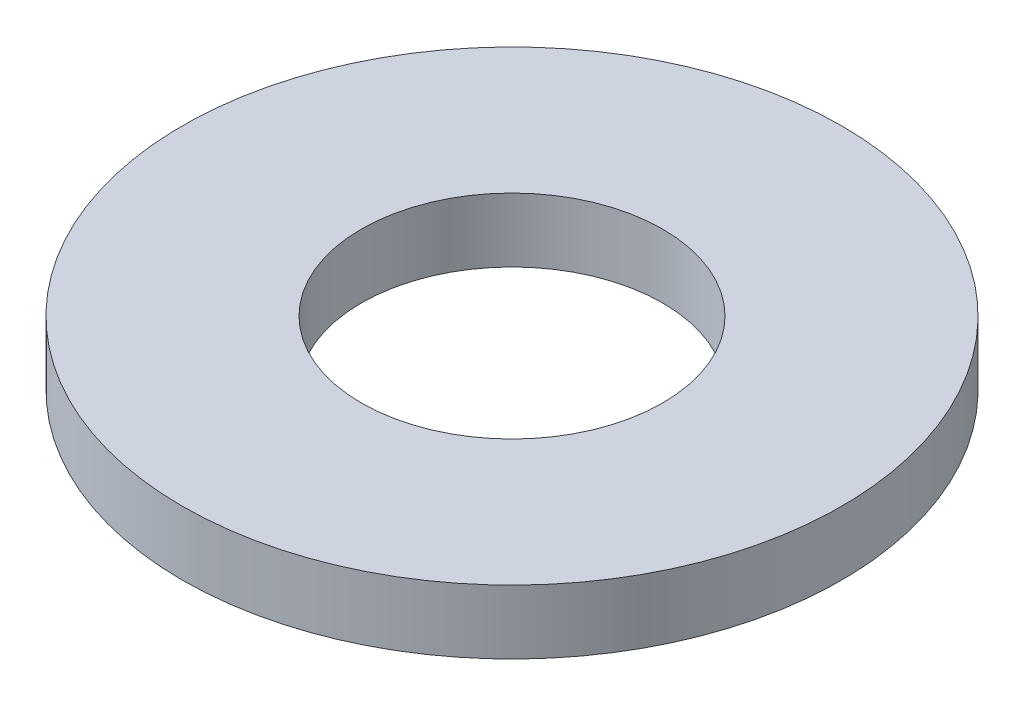
SolidWorks part; units mm, degrees
ref_plane "Front Plane" through (0, 0, 0) normal (0, 0, 1) x (1, 0, 0)
ref_plane "Top Plane" through (0, 0, 0) normal (0, 1, 0) x (1, 0, 0)
ref_plane "Right Plane" through (0, 0, 0) normal (1, 0, 0) x (0, 0, -1)
sketch "Sketch1" plane through (0, 0, 0) normal (0, 1, 0) x (1, 0, 0)
  circle A0 centre (0, 0) radius 87.5
  dimension "FLANGE_OD" = 175
extrude "Boss-Extrude1" add sketch "Sketch1" along normal blind 17
sketch "Sketch2" plane through (0, 0, 0) normal (0, 1, 0) x (1, 0, 0)
  circle A0 centre (0, 0) radius 40
  dimension "BORE_D" = 80
extrude "Cut-Extrude1" cut sketch "Sketch2" along normal through all
sketch "Sketch3" plane through (0, 17, 0) normal (0, 1, 0) x (1, 0, 0)
  circle A0 centre (0, 0) radius 24.5605 construction
  circle A1 centre (-24.5605, 0) radius 7.8849
  dimension "BOLT_D" = 15.7699
  dimension "BOLT_PCD" = 49.121
extrude "Cut-Extrude2" cut sketch "Sketch3" against normal blind 11.8612 rebuild error yes
pattern_circular "CirPattern1" count 5 over 360 rebuild error yes
